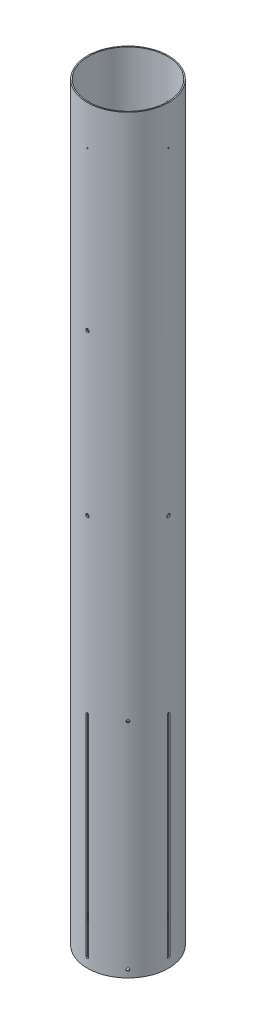
SolidWorks part; units mm, degrees
material "C-Glass Fiber"
ref_plane "Front Plane" through (0, 0, 0) normal (0, 0, 1) x (1, 0, 0)
ref_plane "Top Plane" through (0, 0, 0) normal (0, 1, 0) x (1, 0, 0)
ref_plane "Right Plane" through (0, 0, 0) normal (1, 0, 0) x (0, 0, -1)
sketch "Sustainer Tube Profile" plane through (0, 0, 0) normal (0, 1, 0) x (1, 0, 0)
  circle A0 centre (0, 0) radius 76.2
  circle A1 centre (0, 0) radius 78.359
  dimension "D2" = 156.718
extrude "Sustainer Tube Body" add sketch "Sustainer Tube Profile" along normal blind 1447.8
ref_plane "Plane1" through (0, 0, 78.359) normal (0, 0, 1) x (1, 0, 0)
sketch "Fin Slot Profile" plane through (0, 0, 78.359) normal (0, 0, 1) x (1, 0, 0)
  line L0 (0, 0) -> (0, 1447.8) construction
  line L5 (76.2, 1447.8) -> (-76.2, 1447.8) construction
  line L6 (-78.359, 0) -> (78.359, 0) construction
  line L7 (2.3813, 19.05) -> (-2.3813, 19.05)
  line L8 (0, 19.05) -> (0, 425.45)
  line L9 (2.3813, 425.45) -> (-2.3813, 425.45)
  line L10 (-2.3813, 19.05) -> (-2.3813, 425.45)
  line L11 (2.3813, 19.05) -> (2.3813, 425.45)
  arc A0 (-2.3813, 19.05) -> (2.3812, 19.05) centre (0, 19.05) ccw
  arc A1 (2.3813, 425.45) -> (-2.3812, 425.45) centre (0, 425.45) ccw
  dimension "D1" = 406.4
  dimension "D2" = 19.05
  dimension "D3" = 2.3813
extrude "Fin Slot Cut" cut sketch "Fin Slot Profile" against normal up to surface (2.1962 mm away) contours L7 L11 L9 L8 | L10 L7 L8 L9 | L0 L9 A1 | L9 L0 A1 | A0 L0 L7 | L0 A0 L7 region at (-1.1906, 222.25, 78.359) region at (1.0106, 18.0394, 78.359) region at (1.1906, 222.25, 78.359) region at (-1.0106, 18.0394, 78.359) region at (-1.0106, 426.4606, 78.359) region at (1.0106, 426.4606, 78.359) up to face at (0, 1447.8, 76.2)
pattern_circular "Fin Slot Pattern" count 4 over 360 about axis through (0, 1447.8, 0) along (0, 1, 0) of "Fin Slot Cut"
sketch "Sketch1" plane through (0, 0, 0) normal (0, 0, 1) x (1, 0, 0)
  line L0 (76.2, 1447.8) -> (-76.2, 1447.8) construction
  circle A0 centre (0, 1371.6) radius 1.143
  dimension "D1" = 2.286
  dimension "D2" = 76.2
extrude "Cut-Extrude1" cut sketch "Sketch1" against normal through all both and the other way through all
pattern_circular "CirPattern1" count 4 over 360 about axis through (0, 1447.8, 0) along (0, 1, 0) of "Cut-Extrude1"
sketch "Sketch2" plane through (0, 0, 0) normal (0, 0, 1) x (1, 0, 0)
  line L0 (76.2, 1447.8) -> (-76.2, 1447.8) construction
  circle A0 centre (0, 1066.8) radius 3.175
  dimension "D1" = 6.35
  dimension "D2" = 381
extrude "Cut-Extrude2" cut sketch "Sketch2" against normal through all both and the other way through all
sketch "Sketch3" plane through (0, 0, 0) normal (0, 0, 1) x (1, 0, 0)
  line L0 (78.359, 1447.8) -> (-78.359, 1447.8) construction
  circle A0 centre (0, 756.9962) radius 3.175
  dimension "D2" = 6.35
  dimension "D1" = 690.8038
extrude "Cut-Extrude3" cut sketch "Sketch3" against normal through all both and the other way through all
pattern_circular "CirPattern2" count 4 over 360 about axis through (0, 1447.8, 0) along (0, 1, 0) of "Cut-Extrude3"
ref_plane "Plane2" through (55.4082, 0, 55.4082) normal (0.7071, 0, 0.7071) x (0, -1, 0)
sketch "Sketch4" plane through (55.4082, 0, 55.4082) normal (0.7071, 0, 0.7071) x (0, -1, 0)
  circle A0 centre (-14.0462, 0) radius 2.5794
  circle A1 centre (-429.4429, 0) radius 2.5794
  dimension "D2" = 14.0462
  dimension "D3" = 429.4429
extrude "Cut-Extrude4" cut sketch "Sketch4" against normal up to surface and the other way through all up to face at (-76.1373, 756.269, 3.0906)
ref_plane "Plane3" through (0, 0, 0) normal (0.7071, 0, 0.7071) x (0, -1, 0)
sketch "Sketch7" plane through (0, 0, 0) normal (0, -1, 0) x (1, 0, 0)
  line L0 (0, -76.2) -> (0, 76.2) construction
  line L1 (-76.2, 0) -> (76.2, 0) construction
  point P5 (0, 0)
  point P9 (0, 0)
sketch "Sketch8" plane through (0, 0, 0) normal (0, -1, 0) x (1, 0, 0)
  line L0 (0, -76.2) -> (0, 76.2) construction
  line L1 (0, -76.2) -> (0, 76.2) construction
equation "\"Length\"= 57"
equation "\"Outer Diameter\"= 6.17"
equation "\"Inner Diameter\"= 6"
equation "\"Wall Thickness\"= 0.085"
equation "\"D1@Sustainer Tube Profile\" = \"Inner Diameter\""
equation "\"D2@Sustainer Tube Profile\" = \"Outer Diameter\""
equation "\"D1@Sustainer Tube Body\" = \"Length\""
equation "\"Root Chord\"= 16"
equation "\"Fin Offset\"= 3 / 4"
equation "\"D1@Fin Slot Profile\"=\"Root Chord\" "
equation "\"D2@Fin Slot Profile\" = \"Fin Offset\""
equation "\"Fin Thickness\"= ( 3 / 16 ) / 2"
equation "\"D3@Fin Slot Profile\"=\"Fin Thickness\""
equation "\"Shear Pin Dia\"= 3 / 32"
equation "\"Shear Pin Offset\"= 3"
equation "\"Bulkhead Screw Dia\"= 1 / 4"
equation "\"Bulkhead Screw Offset\"= 24.197 + 3"
equation "\"Rail Button Dia\" = 0.2031"
equation "\"Rail Button Aft Offset\"= 0.553"
equation "\"Rail Button Forward Offset\"= 16.9072"
equation "\"Vent Hole Dia\"= 1 / 4"
equation "\"Vent Hole Offset\"= 15"
equation "\"D1@Sketch2\"=\"Vent Hole Dia\""
equation "\"D2@Sketch2\"=\"Vent Hole Offset\""
equation "\"D1@Sketch3\"=\"Bulkhead Screw Offset\""
equation "\"D2@Sketch3\"=\"Bulkhead Screw Dia\""
equation "\"D1@Sketch4\"=\"Rail Button Dia\""
equation "\"D2@Sketch4\"=\"Rail Button Aft Offset\""
equation "\"D3@Sketch4\"=\"Rail Button Forward Offset\""
